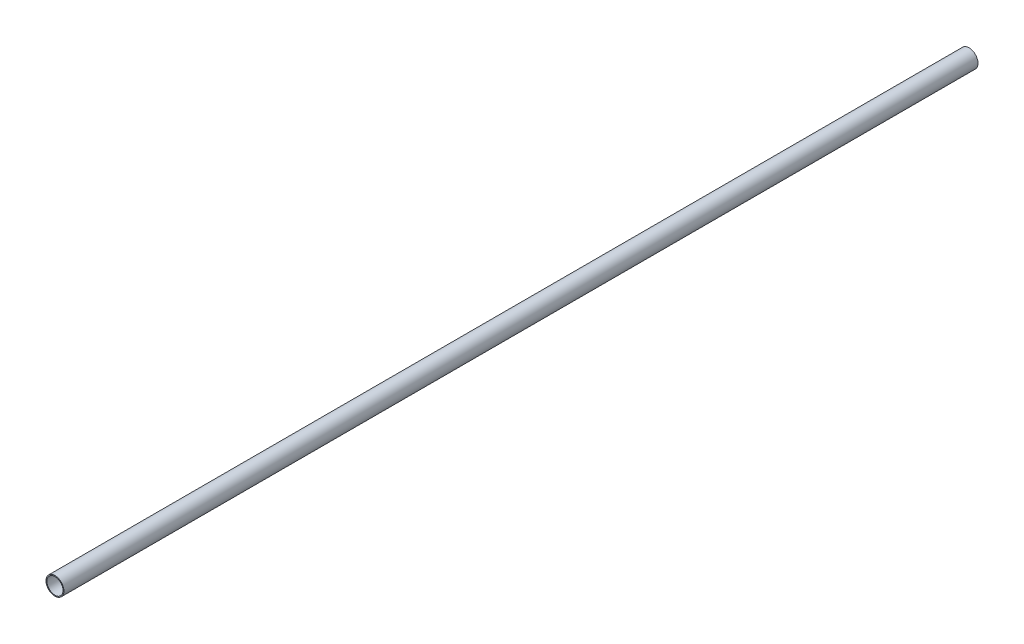
SolidWorks part; units mm, degrees
material "6061 Alloy"
ref_plane "Front Plane" through (0, 0, 0) normal (0, 0, 1) x (1, 0, 0)
ref_plane "Top Plane" through (0, 0, 0) normal (0, 1, 0) x (1, 0, 0)
ref_plane "Right Plane" through (0, 0, 0) normal (1, 0, 0) x (0, 0, -1)
sketch "Sketch1" plane through (0, 0, 0) normal (0, 0, 1) x (1, 0, 0)
  line L0 (0, 0) -> (3.81, 0) construction
  line L1 (3.7368, 0.7433) -> (0, 0) construction
  circle A0 centre (3.7368, 0.7433) radius 3.175
  circle A1 centre (3.7368, 0.7433) radius 2.8575
  dimension "D1" = 6.35
  dimension "D2" = 0.3175
  dimension "D3" = 3.81
  dimension "D4" = 11.25
extrude "Boss-Extrude1" add sketch "Sketch1" along normal blind 311.15 and the other way blind 12.7 contours A0 A1 region at (0.6516, 0.7433, 0)
sketch "Sketch2" [suppressed] plane through (0, 0, 0) normal (0.1951, -0.9808, 0) x (-0.9808, -0.1951, 0)
  line L0 (0, 12.7) -> (0, -2.54)
  line L1 (0.8507, -5.715) -> (9.3093, -20.3656)
  line L2 (10.16, -23.5406) -> (10.16, -58.2395)
  line L3 (8.3001, -62.7296) -> (1.8599, -69.1699)
  line L4 (0, -73.66) -> (0, -312.42)
  line L5 (-6.985, 0) -> (-0.635, 0) construction
  line L7 (0, 0) -> (0, -19.6147) construction
  line L8 (3.175, -76.2) -> (-3.175, -76.2) construction
  line L9 (3.175, -290.83) -> (-3.175, -290.83) construction
  arc A0 (0, -2.54) -> (0.8507, -5.715) centre (6.35, -2.54) ccw
  arc A1 (9.3093, -20.3656) -> (10.16, -23.5406) centre (3.81, -23.5406) cw
  arc A2 (10.16, -58.2395) -> (8.3001, -62.7296) centre (3.81, -58.2395) cw
  arc A3 (1.8599, -69.1699) -> (0, -73.66) centre (6.35, -73.66) ccw
  dimension "D1" = 6.35
  dimension "D2" = 6.35
  dimension "D3" = 6.35
  dimension "D4" = 6.35
  dimension "D5" = 12.7
  dimension "D6" = 10.16
  dimension "D7" = 150
  dimension "D8" = 2.54
  dimension "D9" = 135
  dimension "D10" = 2.54
  dimension "D11" = 21.59
ref_plane "Plane1" [suppressed] through (0, 0, -12.7) normal (0, 0, 1) x (1, 0, 0)
sketch "Sketch3" [suppressed] plane through (0, 0, -12.7) normal (0, 0, 1) x (1, 0, 0)
  circle A0 centre (3.7368, 0.7433) radius 2.54
  circle A1 centre (3.7368, 0.7433) radius 3.175
  circle A2 centre (3.7368, 0.7433) radius 3.175 construction
  dimension "D1" = 6.35
  dimension "D2" = 0.635
sweep "Sweep1" [suppressed] add profiles "Sketch3" path "Sketch2"
